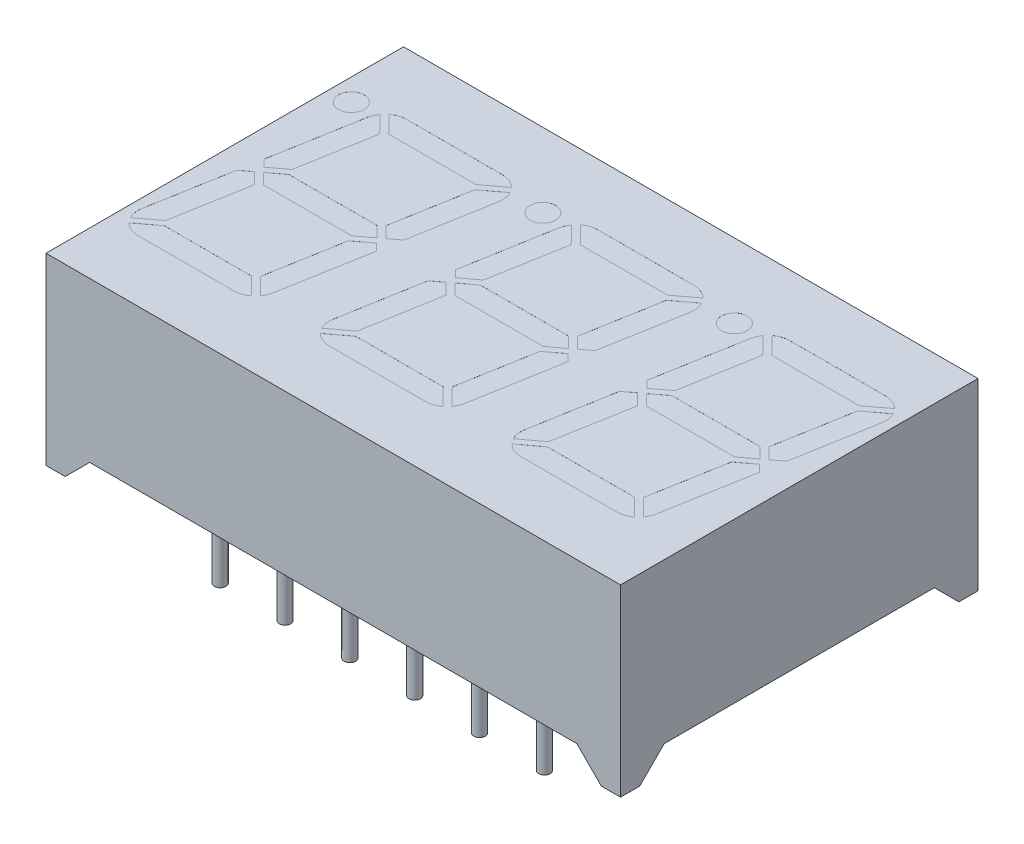
SolidWorks part; units mm, degrees
ref_plane "Front Plane" through (0, 0, 0) normal (0, 0, 1) x (1, 0, 0)
ref_plane "Top Plane" through (0, 0, 0) normal (0, 1, 0) x (1, 0, 0)
ref_plane "Right Plane" through (0, 0, 0) normal (1, 0, 0) x (0, 0, -1)
sketch "Sketch1" plane through (0, 0, 0) normal (0, 1, 0) x (1, 0, 0)
  line L1 (-11.25, -7) -> (11.25, -7)
  line L2 (-11.25, -7) -> (-11.25, 7)
  line L3 (-11.25, 7) -> (11.25, 7)
  line L4 (11.25, -7) -> (11.25, 7)
  line L5 (-11.25, -7) -> (11.25, 7) construction
  line L6 (-11.25, 7) -> (11.25, -7) construction
  point P0 (0, 0)
  dimension "D1" = 22.5
  dimension "D2" = 14
extrude "Boss-Extrude1" add sketch "Sketch1" along normal blind 7.2
sketch "Sketch2" plane through (0, 0, 0) normal (0, 0, 1) x (1, 0, 0)
  line L0 (-10.5, 0) -> (-9.54, 0.96)
  line L1 (-11.25, 0) -> (11.25, 0) construction
  line L2 (-9.54, 0.96) -> (9.54, 0.96)
  line L3 (9.54, 0.96) -> (10.5, 0)
  line L4 (10.5, 0) -> (-10.5, 0)
  line L5 (-11.25, 7.2) -> (-11.25, 0) construction
  line L6 (0, -1000) -> (0, 49000) construction
  point P9 (-8.3351, 1.6907)
  point P12 (9.8352, 0)
  dimension "D1" = 0.75
  dimension "D2" = 45
  dimension "D3" = 0.96
extrude "Cut-Extrude1" cut sketch "Sketch2" against normal through all both and the other way through all
sketch "Sketch3" plane through (0, 0, 0) normal (1, 0, 0) x (0, 0, -1)
  line L0 (0, -1000) -> (0, 49000) construction
  line L1 (-6.25, 0) -> (-5.29, 0.96)
  line L2 (-7, 0) -> (7, 0) construction
  line L3 (-5.29, 0.96) -> (5.29, 0.96)
  line L4 (5.29, 0.96) -> (6.25, 0)
  line L5 (6.25, 0) -> (-6.25, 0)
  line L6 (-7, 7.2) -> (-7, 0) construction
  point P11 (-5.29, 0.96)
  dimension "D1" = 0.75
  dimension "D2" = 0.96
extrude "Cut-Extrude2" cut sketch "Sketch3" against normal through all both and the other way through all
sketch "Sketch4" plane through (0, 0, 0) normal (0, 1, 0) x (1, 0, 0)
  line L8 (11.05, -6.8) -> (11.05, 6.8)
  line L9 (11.05, 6.8) -> (-11.05, 6.8)
  line L10 (-11.05, 6.8) -> (-11.05, -6.8)
  line L11 (-11.05, -6.8) -> (11.05, -6.8)
  line L12 (11.05, -6.8) -> (11.05, 6.8)
  line L13 (11.05, 6.8) -> (-11.05, 6.8)
  line L14 (-11.05, 6.8) -> (-11.05, -6.8)
  line L15 (-11.05, -6.8) -> (11.05, -6.8)
  dimension "D1" = 0.2
extrude "Cut-Extrude3" cut sketch "Sketch4" along normal up to surface (0.96 mm away) up to face at (0, 0.96, 0)
sketch "Sketch5" plane through (0, 0, 0) normal (0, 1, 0) x (1, 0, 0)
  line L0 (-1000, 0) -> (49000, 0) construction
  line L1 (0, -1000) -> (0, 49000) construction
  line L2 (-6.35, 5.08) -> (-3.81, 5.08) construction
  line L3 (-6.35, 5.08) -> (-6.35, -5.08) construction
  circle A0 centre (-6.35, 5.08) radius 0.225
  circle A1 centre (-3.81, 5.08) radius 0.225
  circle A2 centre (-1.27, 5.08) radius 0.225
  circle A3 centre (1.27, 5.08) radius 0.225
  circle A4 centre (3.81, 5.08) radius 0.225
  circle A5 centre (6.35, 5.08) radius 0.225
  circle A6 centre (-3.81, -5.08) radius 0.225
  circle A7 centre (-1.27, -5.08) radius 0.225
  circle A8 centre (1.27, -5.08) radius 0.225
  circle A9 centre (3.81, -5.08) radius 0.225
  circle A10 centre (6.35, -5.08) radius 0.225
  circle A11 centre (-6.35, -5.08) radius 0.225
  dimension "D1" = 0.45
  dimension "D2" = 10.16
  dimension "D3" = 6.35
  dimension "D6" = 2.54
  dimension "D7" = 10.16
  dimension "D4" = 6
  dimension "D5" = 2
extrude "Boss-Extrude2" add sketch "Sketch5" along normal up to surface (0.96 mm away) and the other way blind 2.5 separate body up to face at (0, 0.96, 0)
delete or keep bodies "Body-Delete/Keep 1" type delete bodies bodies 106
sketch "Sketch6" plane through (0, 7.2, 0) normal (0, 1, 0) x (1, 0, 0)
  line L0 (-11.4789, -4.8066) -> (39711.7724, 29842.8805) construction
  line L1 (-8.7275, 4.6) -> (-4.9705, 4.6)
  line L2 (-11.4195, -1.1128) -> (39711.8318, 29846.5744) construction
  line L3 (-5.7773, 0.6786) -> (-34522.4873, 35630.8956) construction
  line L4 (-6.5716, -3.4364) -> (-34519.1788, 35622.5455) construction
  line L5 (-1000, 0) -> (49000, 0) construction
  line L6 (-9.2763, -0.2068) -> (-8691.6852, -49240.5945) construction
  line L7 (-5.7899, -0.0517) -> (-8688.1987, -49240.4393) construction
  line L8 (-11.25, 7) -> (-11.25, -7) construction
  line L9 (-4.1334, 3.6024) -> (-4.6889, 0.4516)
  line L10 (-6.2929, -4.6) -> (-10.05, -4.6)
  line L11 (-10.8871, -3.6024) -> (-10.3315, -0.4516)
  line L12 (-10.0148, -3.5501) -> (-9.4944, -0.5989)
  line L14 (-5.0057, 3.5501) -> (-5.5261, 0.5991)
  line L16 (-1.2275, 4.6) -> (2.5295, 4.6)
  line L17 (2.3441, 3.75) -> (3.1363, 4.3452)
  line L18 (-1.0785, 3.75) -> (2.3441, 3.75)
  line L19 (-1.7374, 4.4301) -> (-1.0785, 3.75)
  line L24 (-1.9134, 4.2521) -> (-1.2583, 3.5759)
  line L25 (-1.773, 0.6564) -> (-1.2583, 3.5759)
  line L26 (-2.671, 0.4588) -> (-2.0646, 3.8976)
  line L27 (-2.671, 0.4588) -> (-2.4035, 0.1827)
  line L28 (-5.1559, 3.75) -> (-4.3637, 4.3452)
  line L29 (-5.0057, 3.5501) -> (-4.2168, 4.143)
  line L30 (-9.2374, 4.4301) -> (-8.5785, 3.75)
  line L31 (-9.4134, 4.2521) -> (-8.7583, 3.5759)
  line L32 (-8.5785, 3.75) -> (-5.1559, 3.75)
  line L33 (-2.4035, 0.1827) -> (-1.773, 0.6564)
  line L34 (-2.2282, 0.0017) -> (-1.6649, 0.425)
  line L35 (-1.8148, -0.425) -> (-2.2282, 0.0017)
  line L36 (-5.5261, 0.5991) -> (-5.0907, 0.1497)
  line L37 (-9.7282, 0.0017) -> (-9.1649, 0.425)
  line L38 (-6.4418, -3.75) -> (-5.783, -4.4301)
  line L39 (-6.2622, -3.5761) -> (-5.6072, -4.2523)
  line L40 (-6.4418, -3.75) -> (-9.8646, -3.75)
  line L41 (1.6443, -0.425) -> (-1.8148, -0.425)
  line L42 (-10.6568, -4.3452) -> (-9.8646, -3.75)
  line L43 (-10.8037, -4.143) -> (-10.0148, -3.5501)
  line L44 (-5.7474, -0.6564) -> (-5.1171, -0.1828)
  line L48 (-5.1171, -0.1828) -> (-4.8495, -0.459)
  line L50 (-4.8495, -0.459) -> (-5.4558, -3.8976)
  line L51 (-10.3315, -0.4516) -> (-9.9296, -0.1497)
  line L52 (-5.7474, -0.6564) -> (-6.2622, -3.5761)
  line L53 (-5.0907, 0.1497) -> (-4.6889, 0.4516)
  line L54 (-10.171, 0.4588) -> (-9.9035, 0.1827)
  line L55 (-9.273, 0.6564) -> (-8.7583, 3.5759)
  line L56 (-9.9035, 0.1827) -> (-9.273, 0.6564)
  line L57 (-10.171, 0.4588) -> (-9.5646, 3.8976)
  line L58 (-9.9296, -0.1497) -> (-9.4944, -0.5989)
  line L59 (-9.1649, 0.425) -> (-5.7058, 0.425)
  line L60 (-5.7058, 0.425) -> (-5.2924, -0.0018)
  line L61 (-5.2924, -0.0018) -> (-5.8557, -0.425)
  line L62 (-5.8557, -0.425) -> (-9.3148, -0.425)
  line L63 (-9.3148, -0.425) -> (-9.7282, 0.0017)
  line L64 (2.2076, -0.0018) -> (1.6443, -0.425)
  line L65 (1.7942, 0.425) -> (2.2076, -0.0018)
  line L66 (-1.6649, 0.425) -> (1.7942, 0.425)
  line L67 (-2.8315, -0.4516) -> (-2.4296, -0.1497)
  line L68 (-2.4296, -0.1497) -> (-1.9944, -0.5989)
  line L69 (-2.5148, -3.5501) -> (-1.9944, -0.5989)
  line L70 (-3.3871, -3.6024) -> (-2.8315, -0.4516)
  line L71 (-3.3037, -4.143) -> (-2.5148, -3.5501)
  line L72 (-3.1568, -4.3452) -> (-2.3646, -3.75)
  line L73 (1.2071, -4.6) -> (-2.55, -4.6)
  line L74 (1.0582, -3.75) -> (-2.3646, -3.75)
  line L75 (1.0582, -3.75) -> (1.717, -4.4301)
  line L76 (1.2378, -3.5761) -> (1.8928, -4.2523)
  line L77 (1.7526, -0.6564) -> (1.2378, -3.5761)
  line L78 (2.6505, -0.459) -> (2.0442, -3.8976)
  line L79 (1.7526, -0.6564) -> (2.3829, -0.1828)
  line L80 (2.3829, -0.1828) -> (2.6505, -0.459)
  line L81 (1.9739, 0.5991) -> (2.4093, 0.1497)
  line L82 (2.4093, 0.1497) -> (2.8111, 0.4516)
  line L83 (3.3666, 3.6024) -> (2.8111, 0.4516)
  line L84 (2.4943, 3.5501) -> (1.9739, 0.5991)
  line L85 (2.4943, 3.5501) -> (3.2832, 4.143)
  line L86 (6.2725, 4.6) -> (10.0295, 4.6)
  line L87 (9.8441, 3.75) -> (10.6363, 4.3452)
  line L88 (6.4215, 3.75) -> (9.8441, 3.75)
  line L89 (5.7626, 4.4301) -> (6.4215, 3.75)
  line L90 (5.5866, 4.2521) -> (6.2417, 3.5759)
  line L91 (5.727, 0.6564) -> (6.2417, 3.5759)
  line L92 (4.829, 0.4588) -> (5.4354, 3.8976)
  line L93 (4.829, 0.4588) -> (5.0965, 0.1827)
  line L94 (5.0965, 0.1827) -> (5.727, 0.6564)
  line L95 (5.2718, 0.0017) -> (5.8351, 0.425)
  line L96 (5.6852, -0.425) -> (5.2718, 0.0017)
  line L97 (9.1443, -0.425) -> (5.6852, -0.425)
  line L98 (9.7076, -0.0018) -> (9.1443, -0.425)
  line L99 (9.2942, 0.425) -> (9.7076, -0.0018)
  line L100 (5.8351, 0.425) -> (9.2942, 0.425)
  line L101 (4.6685, -0.4516) -> (5.0704, -0.1497)
  line L102 (5.0704, -0.1497) -> (5.5056, -0.5989)
  line L103 (4.9852, -3.5501) -> (5.5056, -0.5989)
  line L104 (4.1129, -3.6024) -> (4.6685, -0.4516)
  line L105 (4.1963, -4.143) -> (4.9852, -3.5501)
  line L106 (4.3432, -4.3452) -> (5.1354, -3.75)
  line L107 (8.7071, -4.6) -> (4.95, -4.6)
  line L108 (8.5582, -3.75) -> (5.1354, -3.75)
  line L109 (8.5582, -3.75) -> (9.217, -4.4301)
  line L110 (8.7378, -3.5761) -> (9.3928, -4.2523)
  line L111 (9.2526, -0.6564) -> (8.7378, -3.5761)
  line L112 (10.1505, -0.459) -> (9.5442, -3.8976)
  line L113 (9.2526, -0.6564) -> (9.8829, -0.1828)
  line L114 (9.8829, -0.1828) -> (10.1505, -0.459)
  line L115 (9.4739, 0.5991) -> (9.9093, 0.1497)
  line L116 (9.9093, 0.1497) -> (10.3111, 0.4516)
  line L117 (10.8666, 3.6024) -> (10.3111, 0.4516)
  line L118 (9.9943, 3.5501) -> (9.4739, 0.5991)
  line L119 (9.9943, 3.5501) -> (10.7832, 4.143)
  line L120 (-10.3921, 4.1) -> (-2.8921, 4.1) construction
  arc A1 (-10.05, -4.6) -> (-10.6568, -4.3452) centre (-10.05, -3.75) cw
  arc A2 (-5.4558, -3.8976) -> (-5.6072, -4.2523) centre (-6.2929, -3.75) cw
  arc A3 (-4.9705, 4.6) -> (-4.3637, 4.3452) centre (-4.9705, 3.75) cw
  arc A4 (-8.7275, 4.6) -> (-9.2374, 4.4301) centre (-8.7275, 3.75) ccw
  arc A5 (-9.4134, 4.2521) -> (-9.5646, 3.8976) centre (-8.7275, 3.75) ccw
  arc A6 (-5.783, -4.4301) -> (-6.2929, -4.6) centre (-6.2929, -3.75) cw
  arc A7 (-4.2168, 4.143) -> (-4.1334, 3.6024) centre (-4.9705, 3.75) cw
  arc A8 (-10.8037, -4.143) -> (-10.8871, -3.6024) centre (-10.05, -3.75) cw
  circle A9 centre (-10.3921, 4.1) radius 0.5
  circle A10 centre (-2.8921, 4.1) radius 0.5
  arc A11 (-1.2275, 4.6) -> (-1.7374, 4.4301) centre (-1.2275, 3.75) ccw
  arc A12 (2.5295, 4.6) -> (3.1363, 4.3452) centre (2.5295, 3.75) cw
  arc A13 (-1.9134, 4.2521) -> (-2.0646, 3.8976) centre (-1.2275, 3.75) ccw
  arc A14 (-3.3037, -4.143) -> (-3.3871, -3.6024) centre (-2.55, -3.75) cw
  arc A15 (-2.55, -4.6) -> (-3.1568, -4.3452) centre (-2.55, -3.75) cw
  arc A16 (1.717, -4.4301) -> (1.2071, -4.6) centre (1.2071, -3.75) cw
  arc A17 (2.0442, -3.8976) -> (1.8928, -4.2523) centre (1.2071, -3.75) cw
  arc A18 (3.2832, 4.143) -> (3.3666, 3.6024) centre (2.5295, 3.75) cw
  circle A19 centre (4.6079, 4.1) radius 0.5
  arc A20 (6.2725, 4.6) -> (5.7626, 4.4301) centre (6.2725, 3.75) ccw
  arc A21 (10.0295, 4.6) -> (10.6363, 4.3452) centre (10.0295, 3.75) cw
  arc A22 (5.5866, 4.2521) -> (5.4354, 3.8976) centre (6.2725, 3.75) ccw
  arc A23 (4.1963, -4.143) -> (4.1129, -3.6024) centre (4.95, -3.75) cw
  arc A24 (4.95, -4.6) -> (4.3432, -4.3452) centre (4.95, -3.75) cw
  arc A25 (9.217, -4.4301) -> (8.7071, -4.6) centre (8.7071, -3.75) cw
  arc A26 (9.5442, -3.8976) -> (9.3928, -4.2523) centre (8.7071, -3.75) cw
  arc A27 (10.7832, 4.143) -> (10.8666, 3.6024) centre (10.0295, 3.75) cw
  point P32 (-10.3191, -4.6)
  dimension "D1" = 0.85
  dimension "D8" = 0.25
  dimension "D14" = 5.4
  dimension "D12" = 0.85
  dimension "D15" = 1
  dimension "D2" = 0.85
  dimension "D3" = 0.85
  dimension "D4" = 0.85
  dimension "D5" = 0.85
  dimension "D6" = 0.25
  dimension "D7" = 0.2503
  dimension "D10" = 80
  dimension "D11" = 9.2
  dimension "D13" = 1.2
  dimension "D9" = 0.25
  dimension "D16" = 0.85
  dimension "D18" = 7.5
  dimension "D17" = 3
extrude "Cut-Extrude4" cut sketch "Sketch6" against normal blind 0.001
sketch "Sketch7" plane through (0, 0, -7) normal (0, 0, -1) x (-1, 0, 0)
  line L0 (-11.25, 2.6751) -> (11.25, 2.6751) construction
  line L1 (-11.25, 7.2) -> (-11.25, 0) construction
  line L2 (11.25, 7.2) -> (11.25, 0) construction
  text T0 "TOT-3361" font "OpenGost Type B TT" height 2.5
  point P3 (-11.25, 2.9625)
  point P6 (11.25, 2.9385)
extrude "Cut-Extrude5" cut sketch "Sketch7" against normal blind 0.001
